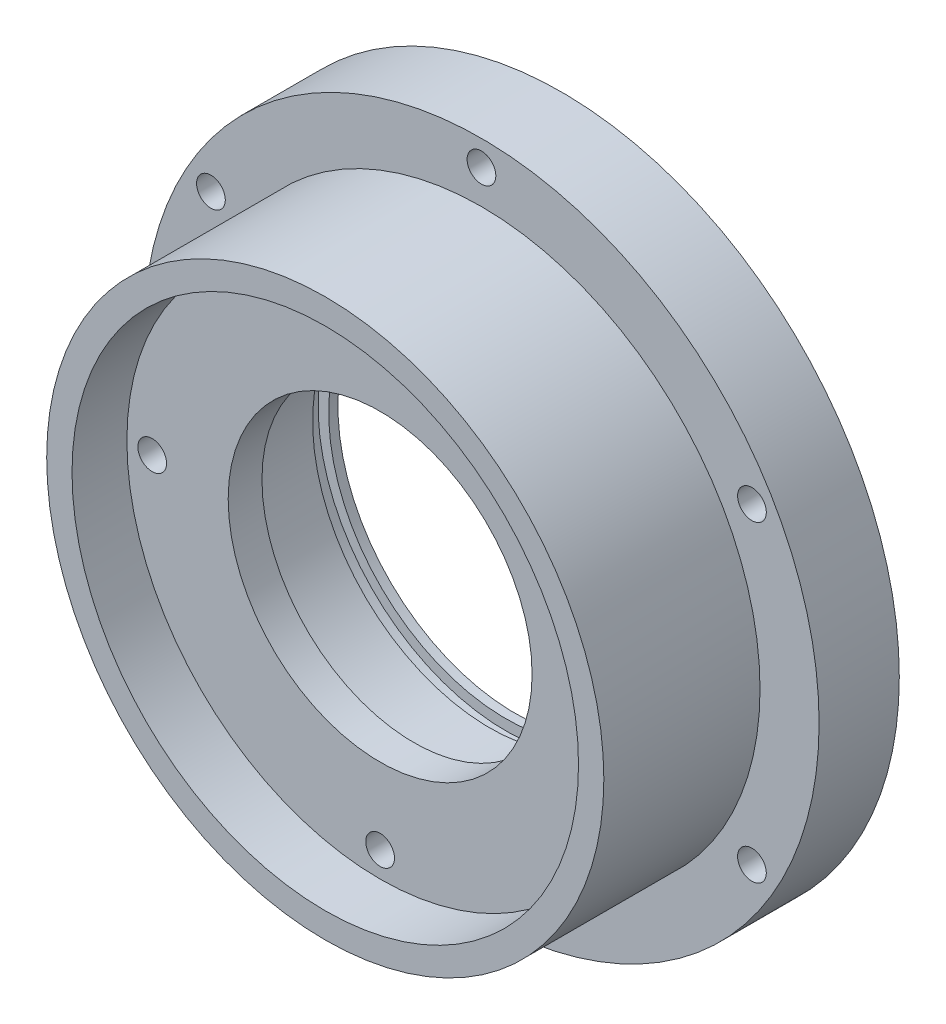
SolidWorks part; units mm, degrees
material "6061-T6 铝合金"
ref_plane "前视基准面" through (0, 0, 0) normal (0, 0, 1) x (1, 0, 0)
ref_plane "上视基准面" through (0, 0, 0) normal (0, 1, 0) x (1, 0, 0)
ref_plane "右视基准面" through (0, 0, 0) normal (1, 0, 0) x (0, 0, -1)
sketch "草图1" plane through (0, 0, 0) normal (1, 0, 0) x (0, 0, -1)
  line L0 (0, 0) -> (23.2925, 0) construction
  line L16 (0, 0) -> (0, 18) construction
  line L18 (0, 30) -> (0, 18)
  line L19 (12, 40) -> (21.5, 40)
  line L20 (21.5, 33) -> (21.5, 40)
  line L21 (0, 18) -> (4, 18)
  line L22 (4, 21) -> (13, 21)
  line L23 (14.9, 21) -> (16, 21)
  line L24 (16, 21) -> (16, 33)
  line L25 (16, 33) -> (21.5, 33)
  line L26 (12, 33) -> (12, 40)
  line L27 (12, 33) -> (-6.5, 33)
  line L28 (4, 18) -> (4, 21)
  line L29 (0, 30) -> (-6.5, 30)
  line L30 (-6.5, 30) -> (-6.5, 33)
  line L31 (13, 21) -> (13, 22.25)
  line L32 (13, 22.25) -> (14.9, 22.25)
  line L33 (14.9, 22.25) -> (14.9, 21)
  dimension "D1" = 40
revolve "旋转1" add sketch "草图1" angle 360 about L0
sketch "草图2" plane through (0, 0, 0) normal (1, 0, 0) x (0, 0, -1)
  line L0 (0, 0) -> (21.5, 0) construction
  line L1 (21.5, -33) -> (21.5, 33) construction
  line L2 (0, 27) -> (21.5, 27) construction
  line L3 (0, 30) -> (0, -30) construction
  line L4 (16, -33) -> (16, 33) construction
  line L5 (4, 24) -> (16, 24)
  line L6 (4, 24) -> (4, 30)
  line L7 (4, 30) -> (16, 30)
  line L8 (16, 24) -> (16, 30)
  line L9 (4, 24) -> (16, 30) construction
  line L10 (4, 30) -> (16, 24) construction
  line L11 (4, 27) -> (16, 27)
  line L13 (4, 27) -> (0, 27)
  line L14 (4, 27) -> (4, 28.7)
  line L15 (4, 28.7) -> (0, 28.7)
  line L16 (0, 27) -> (0, 28.7)
  point P9 (10, 27)
  dimension "D1" = 27
  dimension "D2" = 0
  dimension "D3" = 6
  dimension "D4" = 12
  dimension "D5" = 1.7
revolve "切除-旋转2" cut sketch "草图2" angle 360 about L2 region at (0, 27.85, -2) region at (0, 28.5, -10)
sketch "草图6" plane through (0, 0, -21.5) normal (0, 0, -1) x (-1, 0, 0)
  circle A0 centre (0, 37) radius 1.7
  circle A1 centre (0, 0) radius 40 construction
  dimension "D2" = 3.4
  dimension "D1" = 37
extrude "切除-拉伸1" cut sketch "草图6" against normal through all both and the other way through all
ref_axis "基准轴1" through (0, 0, -22.9868) along (0, 0, 1)
pattern_circular "阵列(圆周)1" count 6 every 60 about axis through (0, 0, -22.9868) along (0, 0, 1) of "切除-拉伸1"
chamfer "倒角1" distance 0.5 angle 45 1 edges at (33, 0, -21.5)
pattern_circular "阵列(圆周)2" count 4 every 90 about axis through (0, 0, -16) along (0, 0, 1) of "切除-旋转2"
